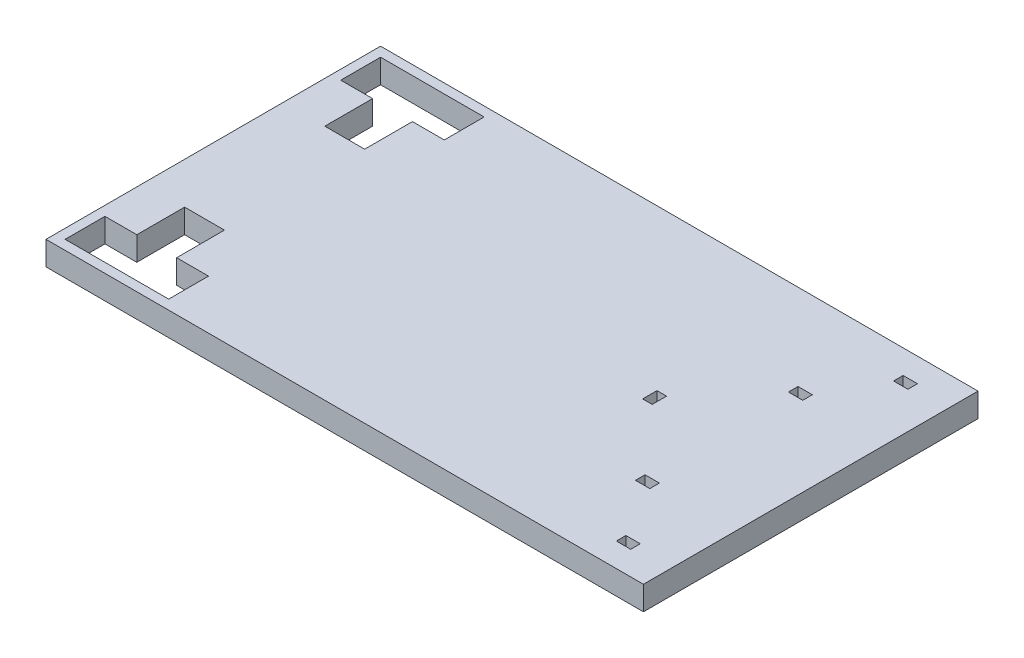
SolidWorks part; units mm, degrees
ref_plane "Front Plane" through (0, 0, 0) normal (0, 0, 1) x (1, 0, 0)
ref_plane "Top Plane" through (0, 0, 0) normal (0, 1, 0) x (1, 0, 0)
ref_plane "Right Plane" through (0, 0, 0) normal (1, 0, 0) x (0, 0, -1)
sketch "Sketch1" plane through (0, 0, 0) normal (0, 1, 0) x (1, 0, 0)
  line L1 (0, 0) -> (375, 0)
  line L2 (0, 0) -> (0, 210)
  line L3 (0, 210) -> (375, 210)
  line L4 (375, 0) -> (375, 210)
  line L5 (352, 189) -> (343, 189)
  line L6 (352, 189) -> (352, 195)
  line L7 (352, 195) -> (343, 195)
  line L8 (343, 189) -> (343, 195)
  line L9 (343, 21) -> (352, 21)
  line L10 (343, 21) -> (343, 15)
  line L11 (343, 15) -> (352, 15)
  line L12 (352, 21) -> (352, 15)
  line L13 (325, 156) -> (316, 156)
  line L14 (325, 156) -> (325, 150)
  line L15 (325, 150) -> (316, 150)
  line L16 (316, 156) -> (316, 150)
  line L17 (325, 54) -> (316, 54)
  line L18 (325, 54) -> (325, 60)
  line L19 (325, 60) -> (316, 60)
  line L20 (316, 54) -> (316, 60)
  line L21 (280, 100.5) -> (274, 100.5)
  line L22 (280, 100.5) -> (280, 109.5)
  line L23 (280, 109.5) -> (274, 109.5)
  line L24 (274, 100.5) -> (274, 109.5)
  line L25 (77, 177.5) -> (257, 177.5)
  line L26 (77, 177.5) -> (77, 32.5)
  line L27 (77, 32.5) -> (257, 32.5)
  line L28 (257, 177.5) -> (257, 32.5)
  line L29 (6, 204) -> (71, 204)
  line L30 (6, 204) -> (6, 179)
  line L31 (6, 179) -> (71, 179)
  line L32 (71, 204) -> (71, 179)
  line L33 (6, 31) -> (71, 31)
  line L34 (6, 31) -> (6, 6)
  line L35 (6, 6) -> (71, 6)
  line L36 (71, 31) -> (71, 6)
  line L37 (26, 31) -> (51, 31)
  line L38 (26, 31) -> (26, 61)
  line L39 (26, 61) -> (51, 61)
  line L40 (51, 31) -> (51, 61)
  line L41 (26, 179) -> (51, 179)
  line L42 (26, 179) -> (26, 149)
  line L43 (26, 149) -> (51, 149)
  line L44 (51, 179) -> (51, 149)
  dimension "D1" = 375
  dimension "D2" = 210
  dimension "D3" = 9
  dimension "D4" = 6
  dimension "D5" = 15
  dimension "D6" = 23
  dimension "D7" = 9
  dimension "D8" = 6
  dimension "D9" = 23
  dimension "D10" = 15
  dimension "D11" = 9
  dimension "D12" = 6
  dimension "D13" = 50
  dimension "D14" = 33
  dimension "D15" = 9
  dimension "D16" = 6
  dimension "D17" = 50
  dimension "D18" = 33
  dimension "D19" = 6
  dimension "D20" = 9
  dimension "D21" = 100.5
  dimension "D22" = 95
  dimension "D23" = 180
  dimension "D24" = 145
  dimension "D25" = 32.5
  dimension "D26" = 77
  dimension "D27" = 65
  dimension "D28" = 25
  dimension "D29" = 6
  dimension "D30" = 6
  dimension "D31" = 65
  dimension "D32" = 25
  dimension "D33" = 6
  dimension "D34" = 6
  dimension "D35" = 25
  dimension "D36" = 30
  dimension "D37" = 20
  dimension "D38" = 30
  dimension "D39" = 20
  dimension "D40" = 20
extrude "Boss-Extrude1" add sketch "Sketch1" along normal blind 15 contours L2 L1 L4 L3
extrude "Cut-Extrude2" cut sketch "Sketch1<5>" along normal blind 34 contours L44 L43 L42 L41
sketch "Sketch1<5>" plane through (0, 0, 0) normal (0, 1, 0) x (1, 0, 0) same geometry as "Sketch1"
extrude "Cut-Extrude3" cut sketch "Sketch1<6>" along normal blind 46 contours L31 L32 L29 L30
sketch "Sketch1<6>" plane through (0, 0, 0) normal (0, 1, 0) x (1, 0, 0) same geometry as "Sketch1"
extrude "Cut-Extrude4" cut sketch "Sketch1<7>" along normal blind 48 contours L35 L36 L33 L34
sketch "Sketch1<7>" plane through (0, 0, 0) normal (0, 1, 0) x (1, 0, 0) same geometry as "Sketch1"
extrude "Cut-Extrude5" cut sketch "Sketch1<8>" along normal blind 45 contours L40 L39 L38 L37
sketch "Sketch1<8>" plane through (0, 0, 0) normal (0, 1, 0) x (1, 0, 0) same geometry as "Sketch1"
extrude "Cut-Extrude6" cut sketch "Sketch1<9>" along normal blind 34 contours L9 L12 L11 L10
sketch "Sketch1<9>" plane through (0, 0, 0) normal (0, 1, 0) x (1, 0, 0) same geometry as "Sketch1"
extrude "Cut-Extrude7" cut sketch "Sketch1<10>" along normal blind 31 contours L17 L20 L19 L18
sketch "Sketch1<10>" plane through (0, 0, 0) normal (0, 1, 0) x (1, 0, 0) same geometry as "Sketch1"
extrude "Cut-Extrude8" cut sketch "Sketch1<11>" along normal blind 34 contours L22 L23 L24 L21
sketch "Sketch1<11>" plane through (0, 0, 0) normal (0, 1, 0) x (1, 0, 0) same geometry as "Sketch1"
extrude "Cut-Extrude9" cut sketch "Sketch1<12>" along normal blind 27 contours L15 L16 L13 L14
sketch "Sketch1<12>" plane through (0, 0, 0) normal (0, 1, 0) x (1, 0, 0) same geometry as "Sketch1"
extrude "Cut-Extrude10" cut sketch "Sketch1<13>" along normal blind 31 contours L5 L8 L7 L6
sketch "Sketch1<13>" plane through (0, 0, 0) normal (0, 1, 0) x (1, 0, 0) same geometry as "Sketch1"
